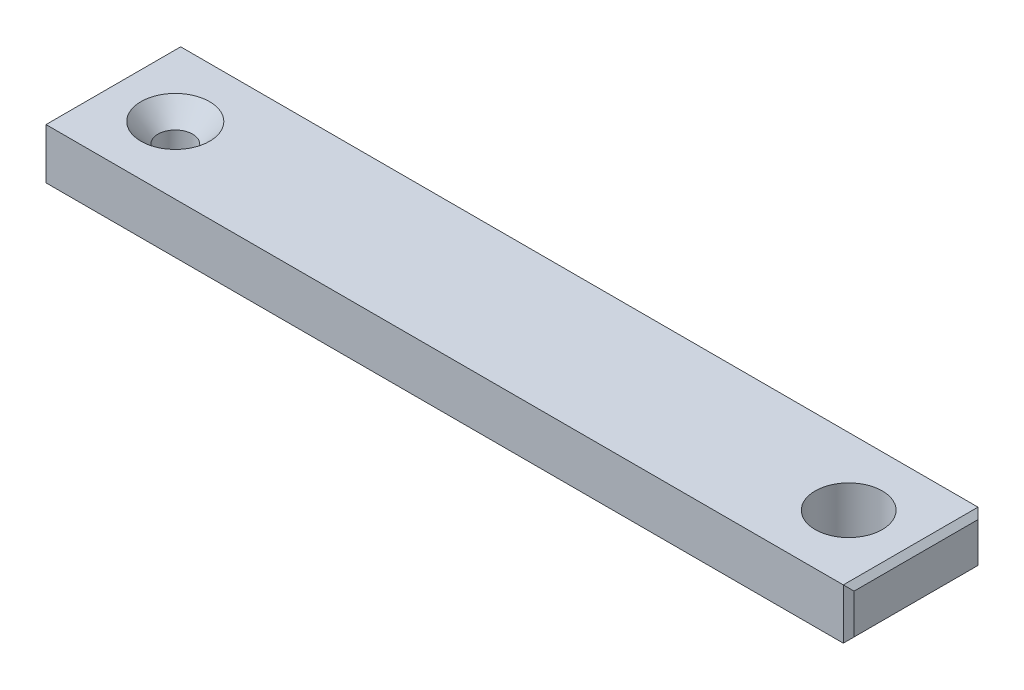
SolidWorks part; units mm, degrees
material "6061-T6 (SS)"
ref_plane "Front Plane" through (0, 0, 0) normal (0, 0, 1) x (1, 0, 0)
ref_plane "Top Plane" through (0, 0, 0) normal (0, 1, 0) x (1, 0, 0)
ref_plane "Right Plane" through (0, 0, 0) normal (1, 0, 0) x (0, 0, -1)
sketch "Sketch1" plane through (0, 0, 0) normal (0, 1, 0) x (1, 0, 0)
  line L0 (-63.5, 0) -> (0, 0) construction
  line L1 (-63.5, 6.35) -> (0, 6.35)
  line L2 (-63.5, -6.35) -> (0, -6.35)
  line L4 (-69.85, 6.35) -> (6.35, 6.35)
  line L5 (-69.85, 6.35) -> (-69.85, -6.35)
  line L6 (-69.85, -6.35) -> (6.35, -6.35)
  line L7 (6.35, 6.35) -> (6.35, -6.35)
  arc A0 (-63.5, 6.35) -> (-63.5, -6.35) centre (-63.5, 0) ccw
  arc A1 (0, -6.35) -> (0, 6.35) centre (0, 0) ccw
  point P2 (-31.75, 0)
  point P9 (-69.85, 0)
  point P10 (6.35, 0)
  dimension "D2" = 76.2
  dimension "D1" = 12.7
extrude "Boss-Extrude2" add sketch "Sketch1" along normal blind 4.7625
sketch "Sketch2" plane through (0, 4.7625, 0) normal (0, 1, 0) x (1, 0, 0)
  line L0 (6.35, 6.35) -> (6.35, -6.35) construction
  line L5 (0, 6.35) -> (0, -6.35)
  line L6 (-69.85, -6.35) -> (6.35, -6.35) construction
  line L7 (-69.85, 6.35) -> (6.35, 6.35) construction
  circle A0 centre (0, 0) radius 3.1623
  dimension "D1" = 6.3246
  dimension "D2" = 6.35
hole_wizard "CSK for #4 Flat Head Socket Cap Screw1" positions "Sketch3" profile "Sketch4" countersink size "#4" standard "ANSI Inch" end condition through all
sketch "Sketch3" plane through (0, 4.7625, 0) normal (0, 1, 0) x (1, 0, 0)
  line L0 (-63.5, 6.35) -> (-63.5, -6.35)
  line L1 (-69.85, 6.35) -> (6.35, 6.35) construction
  line L2 (-69.85, -6.35) -> (6.35, -6.35) construction
  line L4 (-69.85, 6.35) -> (-69.85, -6.35) construction
  point P0 (-63.5, 0)
  dimension "D1" = 6.35
sketch "Sketch4" plane through (-63.5, 4.7625, 0) normal (1, 0, 0) x (0, 0, 1)
  line L0 (0, 0) -> (0, 4.7625)
  line L1 (0, 4.7625) -> (1.6319, 4.7625)
  line L2 (1.6319, 4.7625) -> (1.6319, 1.8481)
  line L3 (1.6319, 1.8481) -> (3.2385, 0)
  line L5 (3.2385, 0) -> (0, 0)
  line L6 (-1.632, 1.8481) -> (-3.2385, 0) construction
  line L11 (0, -6.35) -> (0, 107.95) construction
  dimension "Thru Hole Dia." = 3.2639
  dimension "Thru Hole Depth" = 4.7625
  dimension "Near C'Sink Dia." = 6.477
  dimension "Near C'Sink Angle" = 82
extrude "Cut-Extrude1" cut sketch "Sketch2" against normal through all contours L5 A0 | L5 A0 region at (1.3421, 4.7625, 0) region at (-1.3421, 4.7625, 0)
chamfer "Chamfer1" distance 0.508 angle 45 8 edges at (-69.85, 2.3813, -6.35) (-69.85, 4.7625, 0) (-69.85, 2.3813, 6.35) (-69.85, 0, 0) (6.35, 2.3813, 6.35) (6.35, 4.7625, 0) (6.35, 2.3813, -6.35) (6.35, 0, 0)
